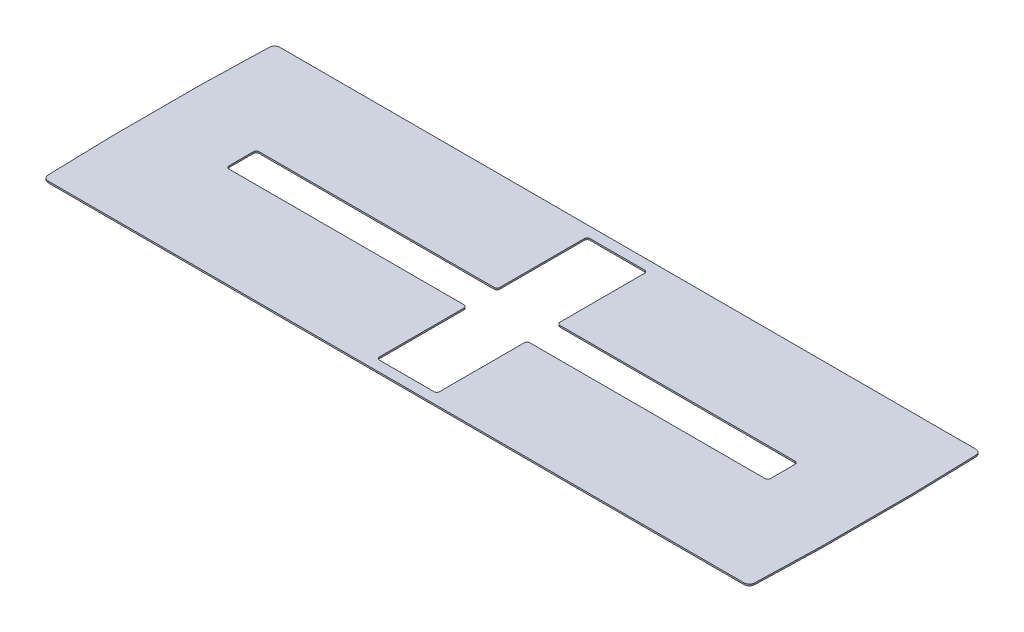
SolidWorks part; units mm, degrees
material "ASTM A36 Steel"
ref_plane "Front Plane" through (0, 0, 0) normal (0, 0, 1) x (1, 0, 0)
ref_plane "Top Plane" through (0, 0, 0) normal (0, 1, 0) x (1, 0, 0)
ref_plane "Right Plane" through (0, 0, 0) normal (1, 0, 0) x (0, 0, -1)
sketch "Sketch1" plane through (0, 0, 0) normal (0, 1, 0) x (1, 0, 0)
  line L1 (596.9, -193.04) -> (-596.9, -193.04)
  line L2 (596.9, -193.04) -> (596.9, 193.04)
  line L3 (596.9, 193.04) -> (-596.9, 193.04)
  line L4 (-596.9, -193.04) -> (-596.9, 193.04)
  line L5 (596.9, -193.04) -> (-596.9, 193.04) construction
  line L6 (596.9, 193.04) -> (-596.9, -193.04) construction
  point P0 (0, 0)
  dimension "D1" = 1193.8
  dimension "D2" = 386.08
extrude "Boss-Extrude1" add sketch "Sketch1" along normal blind 2.667
sketch "Sketch2" plane through (0, 2.667, 0) normal (0, 1, 0) x (1, 0, 0)
  line L0 (592.1375, -38.1) -> (-592.1375, -38.1) construction
  line L1 (592.1375, -38.1) -> (-592.1375, -38.1) construction
  line L2 (592.1375, 38.1) -> (-592.1375, 38.1) construction
  line L3 (592.1375, 38.1) -> (-592.1375, 38.1) construction
  line L4 (0, -38.1) -> (0, 38.1) construction
  line L5 (0, 0) -> (457.2, 0) construction
  line L6 (-457.2, 25.4) -> (-457.2, -25.4)
  line L7 (-457.2, 25.4) -> (457.2, 25.4)
  line L8 (0, 25.4) -> (0, -25.4)
  line L9 (-457.2, -25.4) -> (457.2, -25.4)
  line L10 (457.2, 25.4) -> (457.2, -25.4)
  line L11 (0, 25.4) -> (457.2, -25.4) construction
  line L12 (0, -25.4) -> (457.2, 25.4) construction
  point P8 (228.6, 0)
  dimension "D1" = 457.2
  dimension "D2" = 50.8
extrude "Cut-Extrude1" cut sketch "Sketch2" against normal through all contours L10 L7 L8 L9 | L6 L9 L8 L7 region at (-228.6, 2.667, 0) region at (228.6, 2.667, 0)
sketch "Sketch3" plane through (0, 2.667, 0) normal (0, 1, 0) x (1, 0, 0)
  line L0 (-101.6, -190.6168) -> (-101.6, 190.3832) construction
  line L1 (-101.6, -190.6168) -> (-101.6, 190.3832) construction
  line L2 (101.6, -190.6168) -> (101.6, 190.3832) construction
  line L3 (101.6, -190.6168) -> (101.6, 190.3832) construction
  line L5 (-50.8, 177.8) -> (50.8, 177.8)
  line L6 (-50.8, 177.8) -> (-50.8, -177.8)
  line L7 (-50.8, -177.8) -> (50.8, -177.8)
  line L8 (50.8, 177.8) -> (50.8, -177.8)
  line L9 (-50.8, 177.8) -> (50.8, -177.8) construction
  line L10 (-50.8, -177.8) -> (50.8, 177.8) construction
  point P4 (0, 0)
  dimension "D1" = 355.6
  dimension "D2" = 101.6
extrude "Cut-Extrude2" cut sketch "Sketch3" against normal through all
fillet "Fillet1" radius 4.7625 12 edges at (-457.2, 1.3335, -25.4) (-457.2, 1.3335, 25.4) (457.2, 1.3335, -25.4) (457.2, 1.3335, 25.4) (-50.8, 1.3335, -25.4) (-50.8, 1.3335, 25.4) (50.8, 1.3335, 25.4) (50.8, 1.3335, -25.4) (50.8, 1.3335, 177.8) (-50.8, 1.3335, 177.8) (-50.8, 1.3335, -177.8) (50.8, 1.3335, -177.8)
sketch "Sketch4" plane through (0, 0, 0) normal (0, -1, 0) x (1, 0, 0)
  line L0 (-593.8929, 186.8625) -> (-596.9, 76.2) construction
  line L1 (-593.8929, -186.8625) -> (-596.9, -76.2) construction
  line L2 (-593.8929, 186.8625) -> (-596.9, 76.2)
  line L3 (-593.8929, -186.8625) -> (-596.9, -76.2)
  line L4 (593.8929, 186.8625) -> (596.9, 76.2) construction
  line L5 (593.8929, -186.8625) -> (596.9, -76.2) construction
  line L6 (593.8929, 186.8625) -> (596.9, 76.2)
  line L7 (593.8929, -186.8625) -> (596.9, -76.2)
  arc A0 (-593.8929, -186.8625) -> (-587.5452, -193.04) centre (-587.5452, -186.69) ccw construction
  arc A1 (-587.5452, 193.04) -> (-593.8929, 186.8625) centre (-587.5452, 186.69) ccw construction
  arc A2 (-593.8929, -186.8625) -> (-587.5452, -193.04) centre (-587.5452, -186.69) ccw
  arc A3 (-587.5452, 193.04) -> (-593.8929, 186.8625) centre (-587.5452, 186.69) ccw
  arc A4 (593.8929, 186.8625) -> (587.5452, 193.04) centre (587.5452, 186.69) ccw construction
  arc A5 (587.5452, -193.04) -> (593.8929, -186.8625) centre (587.5452, -186.69) ccw construction
  arc A6 (593.8929, 186.8625) -> (587.5452, 193.04) centre (587.5452, 186.69) ccw
  arc A7 (587.5452, -193.04) -> (593.8929, -186.8625) centre (587.5452, -186.69) ccw
  line M25 (-596.9, 193.04) -> (-596.9, -193.04)
  line M26 (-596.9, -193.04) -> (596.9, -193.04)
  line M27 (596.9, -193.04) -> (596.9, 193.04)
  line M28 (596.9, 193.04) -> (-596.9, 193.04)
extrude "Cut-Extrude3" cut sketch "Sketch4" against normal through all contours A2 L3 M25 M26 | A3 L2 M28 M25 | A6 L6 M27 M28 | A7 L7 M26 M27 region at (-595.6968, 0, 155.6692) region at (-595.6968, 0, -155.6692) region at (595.6968, 0, 155.6692) region at (595.6968, 0, -155.6692)
sketch "Sketch5" plane through (0, 2.667, 0) normal (0, 1, 0) x (1, 0, 0)
  line L0 (587.5452, 195.58) -> (-587.5452, 195.58)
  line L1 (-596.4319, 186.9315) -> (-599.44, 76.2345)
  line L2 (-599.44, 76.2345) -> (-599.44, -76.2345)
  line L3 (-599.44, -76.2345) -> (-596.4319, -186.9315)
  line L4 (-587.5452, -195.58) -> (587.5452, -195.58)
  line L5 (596.4319, -186.9315) -> (599.44, -76.2345)
  line L6 (599.44, -76.2345) -> (599.44, 76.2345)
  line L7 (599.44, 76.2345) -> (596.4319, 186.9315)
  line L8 (596.9, 76.2) -> (593.8929, 186.8625)
  line L9 (587.5452, 193.04) -> (-587.5452, 193.04)
  line L10 (-593.8929, 186.8625) -> (-596.9, 76.2)
  line L11 (-596.9, 76.2) -> (-596.9, -76.2)
  line L12 (-596.9, -76.2) -> (-593.8929, -186.8625)
  line L13 (-587.5452, -193.04) -> (587.5452, -193.04)
  line L14 (593.8929, -186.8625) -> (596.9, -76.2)
  line L15 (596.9, -76.2) -> (596.9, 76.2)
  line L16 (596.9, 76.2) -> (593.8929, 186.8625)
  line L17 (587.5452, 193.04) -> (-587.5452, 193.04)
  line L18 (-593.8929, 186.8625) -> (-596.9, 76.2)
  line L19 (-596.9, 76.2) -> (-596.9, -76.2)
  line L20 (-596.9, -76.2) -> (-593.8929, -186.8625)
  line L21 (-587.5452, -193.04) -> (587.5452, -193.04)
  line L22 (593.8929, -186.8625) -> (596.9, -76.2)
  line L23 (596.9, -76.2) -> (596.9, 76.2)
  arc A0 (-587.5452, 195.58) -> (-596.4319, 186.9315) centre (-587.5452, 186.69) ccw
  arc A1 (-596.4319, -186.9315) -> (-587.5452, -195.58) centre (-587.5452, -186.69) ccw
  arc A2 (587.5452, -195.58) -> (596.4319, -186.9315) centre (587.5452, -186.69) ccw
  arc A3 (596.4319, 186.9315) -> (587.5452, 195.58) centre (587.5452, 186.69) ccw
  arc A4 (593.8929, 186.8625) -> (587.5452, 193.04) centre (587.5452, 186.69) ccw
  arc A5 (-587.5452, 193.04) -> (-593.8929, 186.8625) centre (-587.5452, 186.69) ccw
  arc A6 (-593.8929, -186.8625) -> (-587.5452, -193.04) centre (-587.5452, -186.69) ccw
  arc A7 (587.5452, -193.04) -> (593.8929, -186.8625) centre (587.5452, -186.69) ccw
  arc A8 (593.8929, 186.8625) -> (587.5452, 193.04) centre (587.5452, 186.69) ccw
  arc A9 (-587.5452, 193.04) -> (-593.8929, 186.8625) centre (-587.5452, 186.69) ccw
  arc A10 (-593.8929, -186.8625) -> (-587.5452, -193.04) centre (-587.5452, -186.69) ccw
  arc A11 (587.5452, -193.04) -> (593.8929, -186.8625) centre (587.5452, -186.69) ccw
  dimension "D1" = 0
  dimension "D2" = 2.54
extrude "Boss-Extrude2" add sketch "Sketch5" against normal up to surface (2.667 mm away) up to face at (0, 0, 0)
